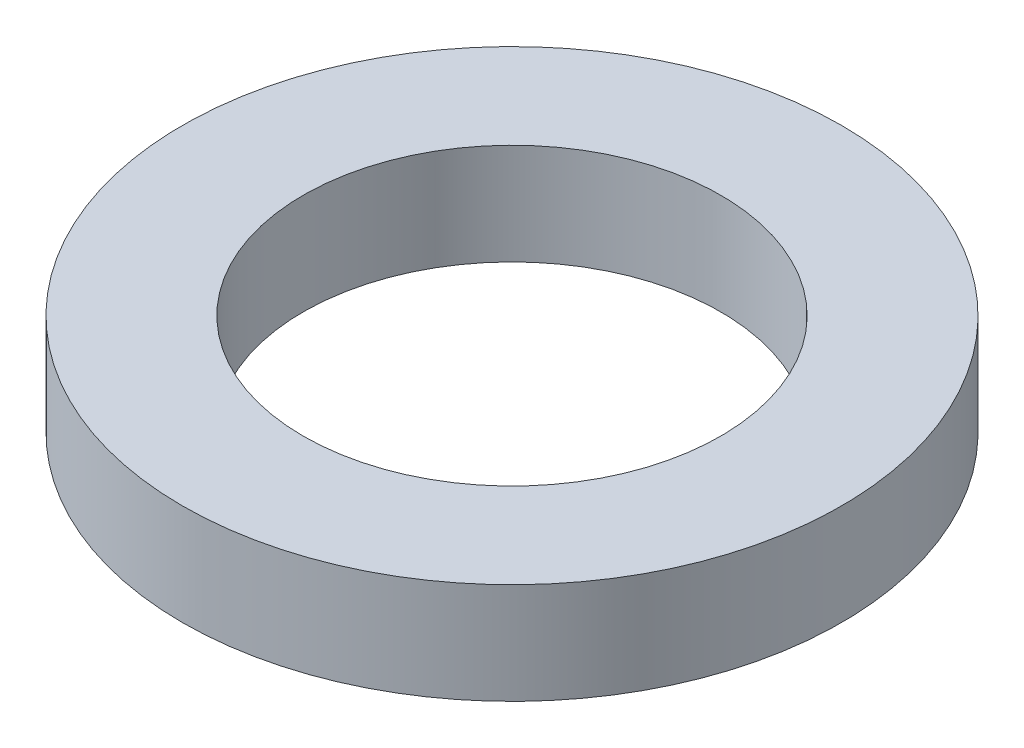
SolidWorks part; units mm, degrees
ref_plane "Front Plane" through (0, 0, 0) normal (0, 0, 1) x (1, 0, 0)
ref_plane "Top Plane" through (0, 0, 0) normal (0, 1, 0) x (1, 0, 0)
ref_plane "Right Plane" through (0, 0, 0) normal (1, 0, 0) x (0, 0, -1)
sketch "Sketch1" plane through (0, 0, 0) normal (0, 1, 0) x (1, 0, 0)
  circle A0 centre (0, 0) radius 75
  dimension "FLANGE_OD" = 150
extrude "Boss-Extrude1" add sketch "Sketch1" along normal blind 23
sketch "Sketch2" plane through (0, 0, 0) normal (0, 1, 0) x (1, 0, 0)
  circle A0 centre (0, 0) radius 47.5
  dimension "BORE_D" = 95
extrude "Cut-Extrude1" cut sketch "Sketch2" along normal through all
sketch "Sketch3" plane through (0, 23, 0) normal (0, 1, 0) x (1, 0, 0)
  circle A0 centre (0, 0) radius 30.0754 construction
  circle A1 centre (-30.0754, 0) radius 4.943
  dimension "BOLT_D" = 9.886
  dimension "BOLT_PCD" = 60.1507
extrude "Cut-Extrude2" cut sketch "Sketch3" against normal blind 20.4252 rebuild error yes
pattern_circular "CirPattern1" count 8 over 360 rebuild error yes
